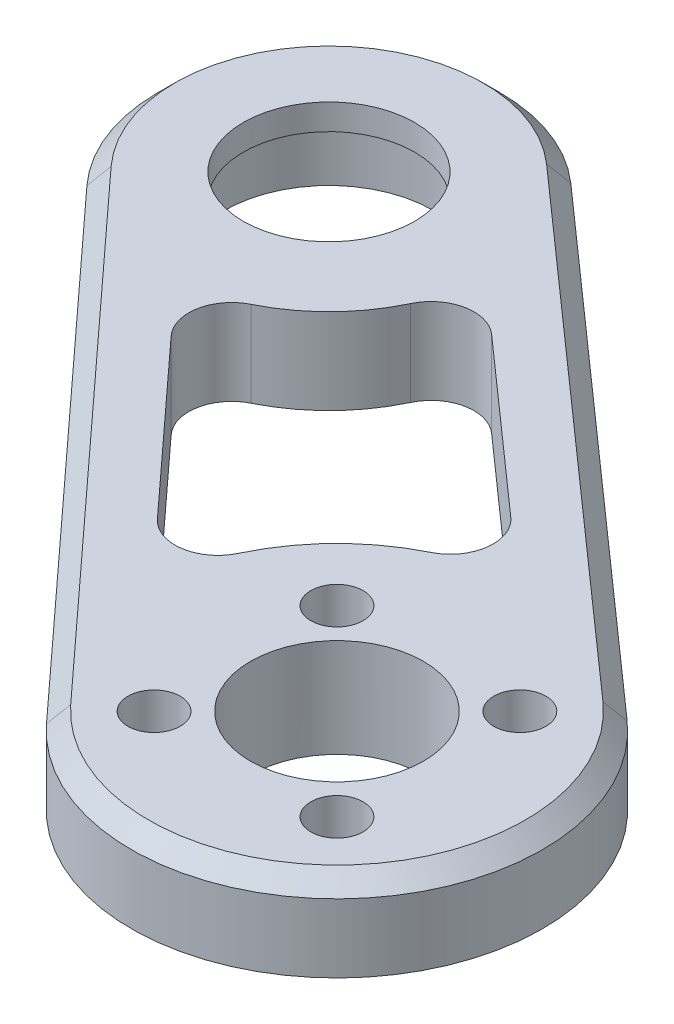
SolidWorks part; units mm, degrees
material "PLA Infill"
ref_plane "Front Plane" through (0, 0, 0) normal (0, 0, 1) x (1, 0, 0)
ref_plane "Top Plane" through (0, 0, 0) normal (0, 1, 0) x (1, 0, 0)
ref_plane "Right Plane" through (0, 0, 0) normal (1, 0, 0) x (0, 0, -1)
sketch "Sketch1" plane through (0, 0, 0) normal (0, 1, 0) x (1, 0, 0)
  line L0 (0, 0) -> (55, 54.0672) construction
  line L1 (55, 54.0672) -> (-55, 54.0672) construction
  line L2 (-55, 54.0672) -> (0, 0) construction
  line L3 (-69.7415, 40.551) -> (-17.6898, -16.2194)
  line L4 (-41.7379, 69.0378) -> (15.9145, 17.9646)
  line L5 (-47.6255, 28.2677) -> (-29.9271, 8.9649)
  line L6 (-29.0781, 47.135) -> (-9.4754, 29.7694)
  circle A0 centre (0, 0) radius 10.1
  circle A1 centre (-55, 54.0672) radius 10
  circle A2 centre (0, 0) radius 24 construction
  circle A3 centre (-55, 54.0672) radius 20 construction
  arc A4 (-69.7415, 40.551) -> (-41.7379, 69.0378) centre (-55, 54.0672) cw
  arc A5 (-17.6898, -16.2194) -> (15.9145, 17.9646) centre (0, 0) ccw
  arc A6 (-46.1521, 36.1308) -> (-36.9149, 45.5274) centre (-55, 54.0672) ccw
  arc A7 (-21.7173, 10.2157) -> (-10.5856, 21.5394) centre (0, 0) cw
  arc A8 (-29.9271, 8.9649) -> (-21.7173, 10.2157) centre (-26.2417, 12.3439) ccw
  arc A9 (-9.4754, 29.7694) -> (-10.5856, 21.5394) centre (-12.7909, 26.0268) cw
  arc A10 (-29.0781, 47.135) -> (-36.9149, 45.5274) centre (-32.3936, 43.3924) ccw
  arc A11 (-47.6255, 28.2677) -> (-46.1521, 36.1308) centre (-43.9401, 31.6467) cw
  point P22 (-23.8825, 2.3723)
  point P25 (-2.7804, 23.8384)
  point P28 (-35.0663, 52.4399)
  point P31 (-53.032, 34.1643)
  dimension "D3" = 20.2
  dimension "D4" = 20
  dimension "D5" = 48
  dimension "D6" = 40
  dimension "D9" = 5
  dimension "D1" = 77.125
  dimension "D2" = 110
  dimension "D7" = 8
  dimension "D8" = 8
extrude "Main Body" add sketch "Sketch1" along normal blind 10
sketch "Sketch2" plane through (0, 0, 0) normal (0, -1, 0) x (1, 0, 0)
  circle A0 centre (-55, -54.0672) radius 10 construction
  circle A1 centre (-55, -54.0672) radius 10 construction
  circle A2 centre (-55, -54.0672) radius 12.2
  dimension "D1" = 24.4
extrude "Bearing Recess" cut sketch "Sketch2" against normal blind 7
sketch "Sketch3" plane through (0, 0, 0) normal (0, -1, 0) x (1, 0, 0)
  circle A0 centre (0, 0) radius 21.5
  circle A1 centre (0, 0) radius 10.1
  circle A2 centre (0, 0) radius 10.1 construction
  dimension "D1" = 43
extrude "Standoff Section" add sketch "Sketch3" along normal blind 1.5
sketch "Sketch4" plane through (0, -1.5, 0) normal (0, -1, 0) x (1, 0, 0)
  line L0 (0, 0) -> (50000, 0) construction
  line L1 (55, -54.0672) -> (-55, -54.0672) construction
  line L2 (-10.6773, 10.6773) -> (0, 0) construction
  circle A0 centre (-10.6773, 10.6773) radius 3.05
  circle A2 centre (10.6773, 10.6773) radius 3.05
  circle A3 centre (10.6773, -10.6773) radius 3.05
  circle A4 centre (-10.6773, -10.6773) radius 3.05
  dimension "D1" = 6.1
  dimension "D2" = 15.1
  dimension "D3" = 45
  dimension "D4" = 4
extrude "M6 Bolt holes" cut sketch "Sketch4" against normal through all
chamfer "Chamfer1" distance 2 angle 45 4 edges at (17.1151, 10, 16.8248) (-12.9117, 10, -43.5012) (-43.7157, 10, -12.1658) (-69.2626, 10, -68.0879)
